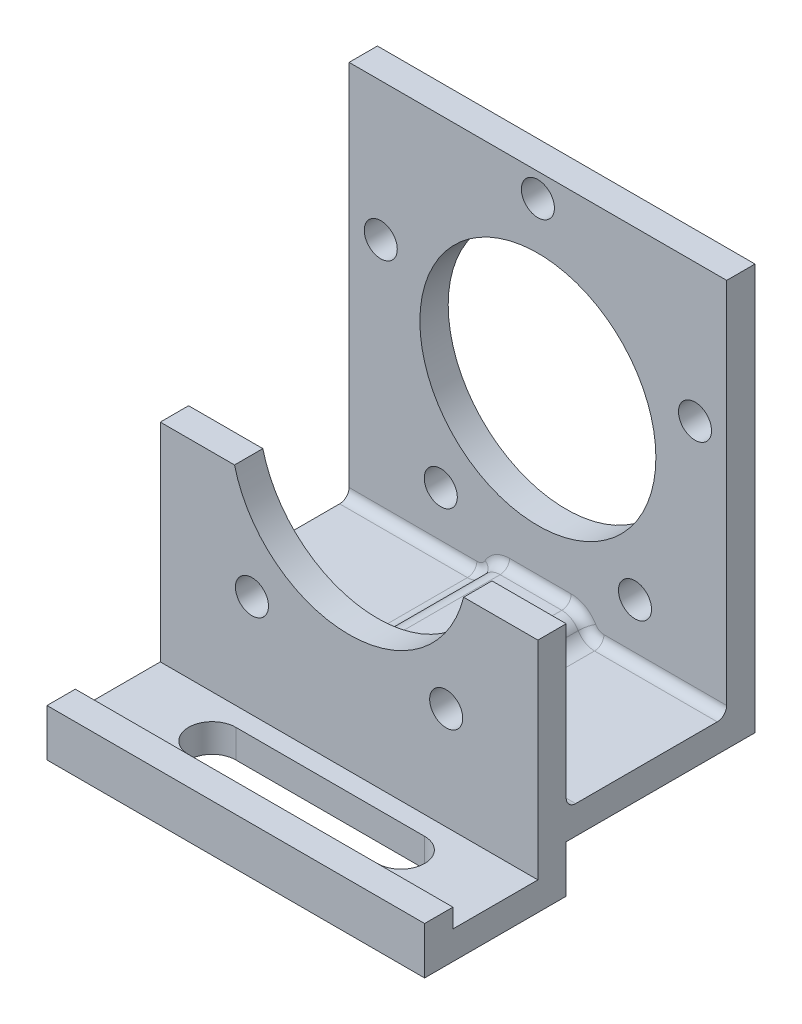
SolidWorks part; units mm, degrees
ref_plane "Front" through (0, 0, 0) normal (0, 0, 1) x (1, 0, 0)
ref_plane "Top" through (0, 0, 0) normal (0, 1, 0) x (1, 0, 0)
ref_plane "Right" through (0, 0, 0) normal (1, 0, 0) x (0, 0, -1)
sketch "Sketch1" plane through (0, 0, 0) normal (0, 0, 1) x (1, 0, 0)
  line L0 (-20, 40) -> (-20, 0)
  line L1 (-20, 0) -> (20, 0)
  line L3 (-20, 40) -> (20, 40)
  line L4 (20, 0) -> (20, 40)
  point P4 (0, 0)
  dimension "D1" = 40
extrude "Boss-Extrude1" add sketch "Sketch1" against normal blind 3
sketch "Sketch3" plane through (0, 0, 0) normal (1, 0, 0) x (0, 0, -1)
  line L0 (3, 0) -> (-17, 0)
  dimension "D1" = 20
extrude "Extrude-Thin1" add sketch "Sketch3" along normal mid plane 40 thin thin type one direction reverse wall 3
sketch "Sketch4" plane through (0, 0, 0) normal (0, 1, 0) x (1, 0, 0)
  line L1 (20, 0) -> (-20, 0) construction
  line L2 (-5, 0) -> (5, 0)
  line L3 (-5, 0) -> (-5, -17)
  line L4 (-5, -17) -> (5, -17)
  line L5 (5, 0) -> (5, -17)
  line L6 (20, -17) -> (-20, -17) construction
  dimension "D1" = 10
extrude "Boss-Extrude2" add sketch "Sketch4" along normal blind 2
sketch "Sketch5" plane through (0, 0, 0) normal (1, 0, 0) x (0, 0, -1)
  line L0 (-17, 17) -> (-17, -8)
  line L1 (-17, -8) -> (-32, -8)
  line L2 (-32, -8) -> (-32, -3)
  line L6 (-17, -3) -> (-17, 0) construction
  line L15 (3, -3) -> (-17, -3) construction
  point P6 (-16.4719, -0.387)
  point P9 (-16.1772, -3)
  point P10 (-3.158, -6.755)
  point P14 (-13.2672, -4.764)
  point P15 (-13.7563, 0)
  point P20 (-9.0608, -3)
  point P22 (-15.4213, -1.208)
  dimension "D1" = 20
  dimension "D2" = 15
  dimension "D3" = 5
  dimension "D4" = 25
extrude "Extrude-Thin2" add sketch "Sketch5" along normal mid plane 40 thin thin type one direction wall 3
sketch "Sketch6" plane through (0, 0, 32) normal (0, 0, 1) x (1, 0, 0)
  line L0 (20, 0) -> (20, 40) construction
  circle A0 centre (0, 20) radius 12.5
  point P8 (20, 20)
  dimension "D1" = 25
extrude "Cut-Extrude1" cut sketch "Sketch6" against normal through all
sketch "Sketch7" plane through (0, 0, 0) normal (0, 0, 1) x (1, 0, 0)
  circle A0 centre (0, 20) radius 17.5 construction
  circle A1 centre (0, 37.5) radius 1.75
  dimension "D1" = 3.5
  dimension "D2" = 35
  dimension "D3" = 20
extrude "Cut-Extrude2" cut sketch "Sketch7" against normal through all
pattern_circular "CirPattern1" count 5 over 360 about axis through (0, 20, 0) along (0, 0, -1) of "Cut-Extrude2"
sketch "Sketch8" plane through (0, 0, 20) normal (0, 0, 1) x (1, 0, 0)
  circle A0 centre (10.2862, 5.8422) radius 1.75
  circle A2 centre (10.2862, 5.8422) radius 1.75 construction
  dimension "D1" = 3.5
extrude "Cut-Extrude3" cut sketch "Sketch8" against normal blind 10
sketch "Sketch9" plane through (0, 0, 20) normal (0, 0, 1) x (1, 0, 0)
  circle A0 centre (-10.2862, 5.8422) radius 1.75
  circle A1 centre (-10.2862, 5.8422) radius 1.75 construction
extrude "Cut-Extrude4" cut sketch "Sketch9" against normal blind 10
sketch "Sketch10" plane through (0, -5, 0) normal (0, 1, 0) x (1, 0, 0)
  line L0 (-10, -24.5) -> (10, -24.5) construction
  line L1 (-10, -22) -> (10, -22)
  line L2 (-10, -27) -> (10, -27)
  line L3 (20, -20) -> (-20, -20) construction
  arc A0 (-10, -22) -> (-10, -27) centre (-10, -24.5) ccw
  arc A1 (10, -27) -> (10, -22) centre (10, -24.5) ccw
  point P2 (0, -24.5)
  point P9 (-12.5, -24.5)
  point P10 (12.5, -24.5)
  dimension "D1" = 5
  dimension "D2" = 4.5
  dimension "D3" = 25
extrude "Cut-Extrude5" cut sketch "Sketch10" against normal through all
fillet "Fillet1" radius 2 1 edges at (5, 0, 8.5)
fillet "Fillet3" radius 2 1 edges at (5, 2, 8.5)
fillet "Fillet4" radius 2 1 edges at (-5, 2, 8.5)
fillet "Fillet5" radius 2 1 edges at (-5, 0, 8.5)
fillet "Fillet2" radius 1 14 edges at (13.5, 0, 0) (6, 0.2679, 0) (0.2679, 2, 0) (13.5, 0, 17) (6, 0.2679, 17) (0.2679, 2, 17) (4.5359, 1.7321, 17) (-4, 1.7321, 17) (-5.4641, 0.2679, 17) (4.5359, 1.7321, 0) (-4, 1.7321, 0) (-5.4641, 0.2679, 0) (-13.2321, 0, 17) (-13.2321, 0, 0)
